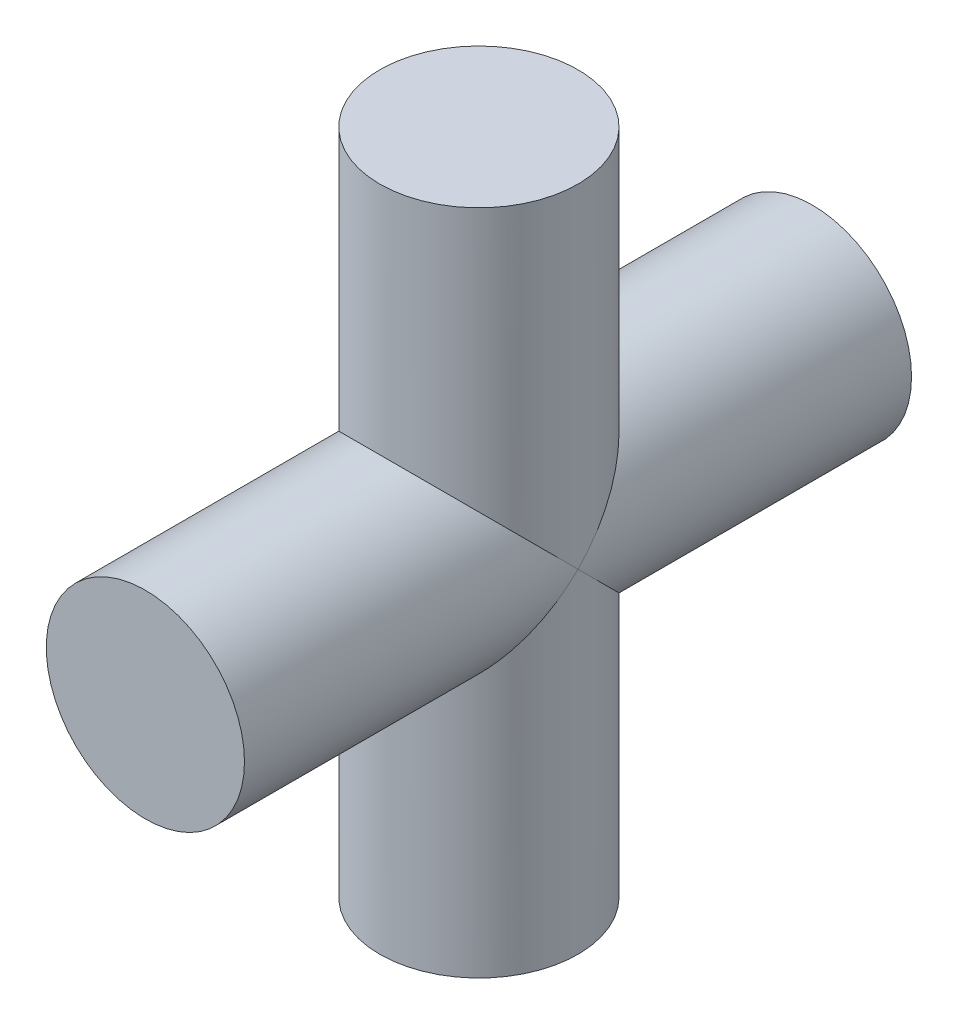
SolidWorks part; units mm, degrees
material "Brass"
ref_plane "Front Plane" through (0, 0, 0) normal (0, 0, 1) x (1, 0, 0)
ref_plane "Top Plane" through (0, 0, 0) normal (0, 1, 0) x (1, 0, 0)
ref_plane "Right Plane" through (0, 0, 0) normal (1, 0, 0) x (0, 0, -1)
sketch "Sketch1" plane through (0, 0, 0) normal (0, 1, 0) x (1, 0, 0)
  circle A0 centre (0, 0) radius 8
  dimension "D1" = 16
extrude "Boss-Extrude1" add sketch "Sketch1" along normal blind 26.924 and the other way blind 26.924
sketch "Sketch2" plane through (0, 0, 0) normal (0, 0, 1) x (1, 0, 0)
  circle A0 centre (0, 0) radius 8
extrude "Boss-Extrude2" add sketch "Sketch2" along normal blind 26.924 and the other way blind 26.924
